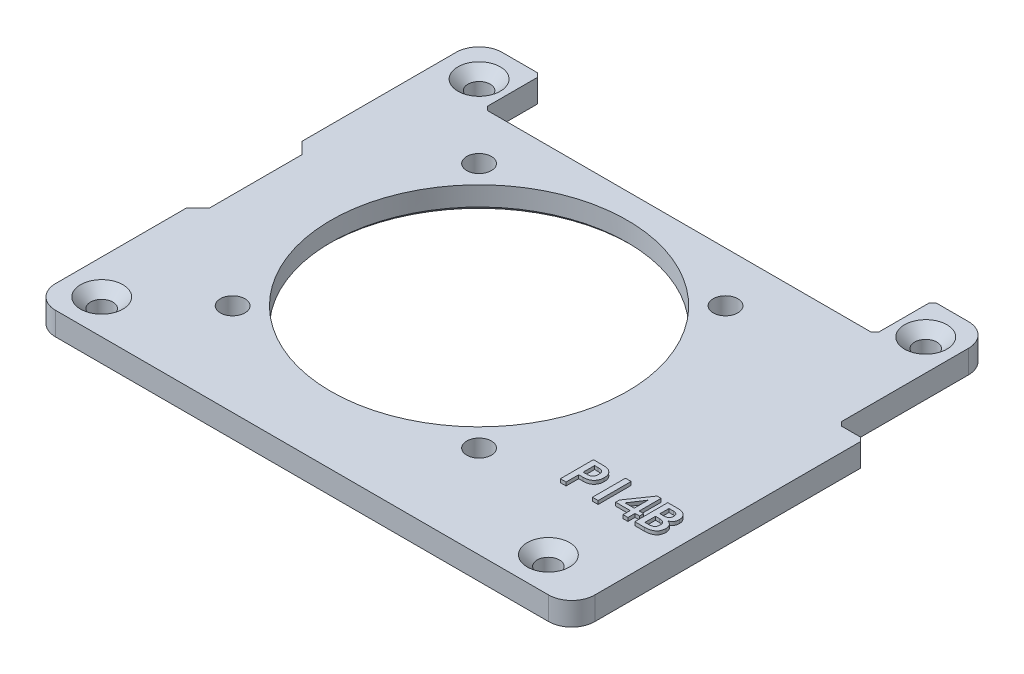
SolidWorks part; units mm, degrees
ref_plane "前视基准面" through (0, 0, 0) normal (0, 0, 1) x (1, 0, 0)
ref_plane "上视基准面" through (0, 0, 0) normal (0, 1, 0) x (1, 0, 0)
ref_plane "右视基准面" through (0, 0, 0) normal (1, 0, 0) x (0, 0, -1)
sketch "草图1" plane through (0, 0, 0) normal (0, 1, 0) x (1, 0, 0)
  line L0 (70.03, 0) -> (70.03, 38)
  line L1 (0, 0) -> (70.03, 0)
  line L2 (0, 0) -> (0, 58)
  line L3 (0, 58) -> (66.55, 58)
  line L4 (70.03, 38) -> (66.55, 38)
  line L5 (66.55, 38) -> (66.55, 58)
  dimension "D3" = 66.55
  dimension "D4" = 20
  dimension "D1" = 70.03
  dimension "D2" = 58
extrude "凸台-拉伸1" add sketch "草图1" along normal blind 3
hole_wizard "M2.5 锥坑平头螺钉的锥形沉头孔1" positions "草图5" profile "草图4" countersink size "M2.5" standard "DIN" end condition through all
sketch "草图5" plane through (0, 3, 0) normal (0, 1, 0) x (1, 0, 0)
  point P0 (4.5, 4.5)
  point P2 (4.5, 53.5)
  point P4 (62.5, 53.5)
  point P6 (62.5, 4.5)
  dimension "D1" = 4.5
  dimension "D2" = 4.5
  dimension "D3" = 58
  dimension "D4" = 49
sketch "草图4" plane through (4.5, 3, -4.5) normal (1, 0, 0) x (0, 0, 1)
  line L0 (0, 0) -> (0, 3)
  line L1 (0, 3) -> (1.45, 3)
  line L2 (1.45, 3) -> (1.45, 1.3)
  line L3 (1.45, 1.3) -> (2.75, 0)
  line L5 (2.75, 0) -> (0, 0)
  line L6 (-1.45, 1.3) -> (-2.75, 0) construction
  line L11 (0, -6.35) -> (0, 107.95) construction
  dimension "通孔孔直径" = 2.9
  dimension "通孔孔深度" = 3
  dimension "近端锥形沉头孔直径" = 5.5
  dimension "近端锥形沉头孔角度" = 90
sketch "草图7" plane through (0, 3, 0) normal (0, 1, 0) x (1, 0, 0)
  line L0 (66.55, 58) -> (0, 58) construction
  line L1 (8.1, 58) -> (58.9, 58)
  line L2 (8.1, 58) -> (8.1, 50.5)
  line L3 (8.1, 50.5) -> (58.9, 50.5)
  line L4 (58.9, 58) -> (58.9, 50.5)
  line L5 (0, 58) -> (0, 0) construction
  dimension "D1" = 8.1
  dimension "D2" = 50.8
  dimension "D3" = 7.5
extrude "切除-拉伸1" cut sketch "草图7" against normal through all
sketch "草图8" plane through (0, 3, 0) normal (0, 1, 0) x (1, 0, 0)
  line L1 (14, 44) -> (46, 44) construction
  line L2 (14, 44) -> (14, 12) construction
  line L3 (14, 12) -> (46, 12) construction
  line L4 (46, 44) -> (46, 12) construction
  line L5 (14, 44) -> (46, 12) construction
  line L6 (14, 12) -> (46, 44) construction
  circle A0 centre (30, 28) radius 19.25
  circle A1 centre (14, 44) radius 1.6
  circle A2 centre (46, 44) radius 1.6
  circle A3 centre (14, 12) radius 1.6
  circle A4 centre (46, 12) radius 1.6
  dimension "D1" = 38.5
  dimension "D6" = 3.2
  dimension "D7" = 3.2
  dimension "D8" = 3.2
  dimension "D9" = 3.2
  dimension "D2" = 30
  dimension "D3" = 28
  dimension "D4" = 32
  dimension "D5" = 32
extrude "切除-拉伸2" cut sketch "草图8" against normal through all
fillet "圆角2" radius 3 4 edges at (66.55, 1.5, -58) (0, 1.5, -58) (0, 1.5, 0) (70.03, 1.5, 0)
chamfer "倒角1" distance 0.5 angle 45 6 edges at (66.55, 1.5, -38) (70.03, 1.5, -38) (58.9, 1.5, -58) (8.1, 1.5, -58) (8.1, 1.5, -50.5) (58.9, 1.5, -50.5)
chamfer "倒角2" distance 0.5 angle 45 1 edges at (30, 0, -8.75)
sketch "草图9" plane through (0, 3, 0) normal (0, 1, 0) x (1, 0, 0)
  line L0 (0, 55) -> (0, 3) construction
  line L1 (0, 20) -> (1.5, 20)
  line L2 (0, 20) -> (0, 35)
  line L3 (0, 35) -> (1.5, 35)
  line L4 (1.5, 20) -> (1.5, 35)
  line L5 (3, 0) -> (67.03, 0) construction
  dimension "D1" = 20
  dimension "D2" = 15
  dimension "D3" = 1.5
extrude "切除-拉伸3" cut sketch "草图9" against normal through all
chamfer "倒角3" distance 1.5 angle 45 2 edges at (1.5, 1.5, -20) (1.5, 1.5, -35)
sketch "草图10" plane through (0, 3, 0) normal (0, 1, 0) x (1, 0, 0)
  text T0 "<b>PI4B</b>" font "黑体" height in points 14
extrude "凸台-拉伸2" add sketch "草图10" along normal blind 0.45
